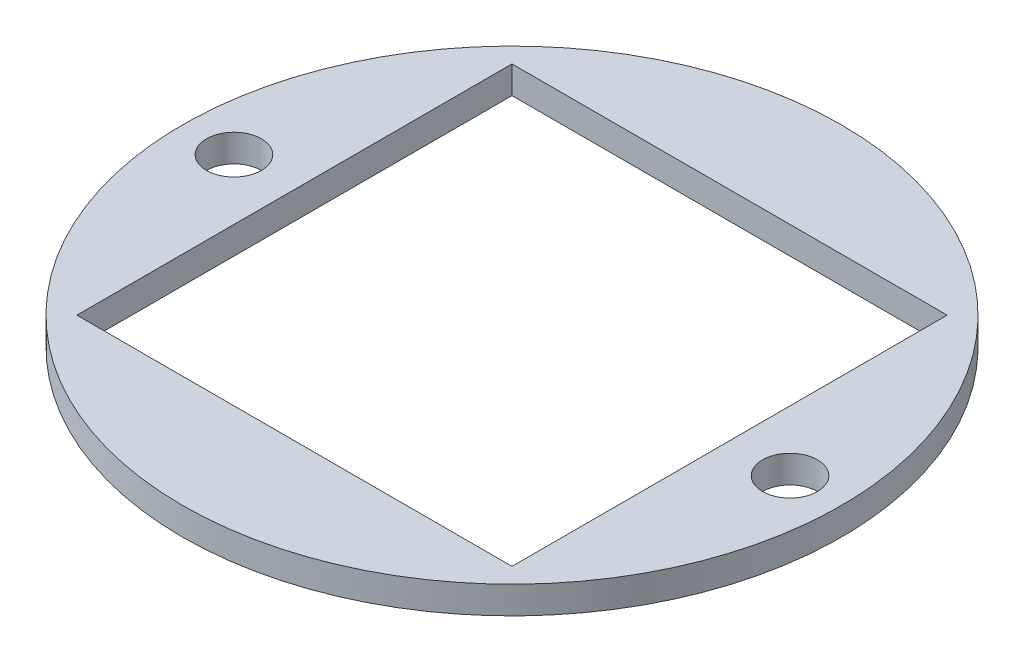
SolidWorks part; units mm, degrees
ref_plane "Front Plane" through (0, 0, 0) normal (0, 0, 1) x (1, 0, 0)
ref_plane "Top Plane" through (0, 0, 0) normal (0, 1, 0) x (1, 0, 0)
ref_plane "Right Plane" through (0, 0, 0) normal (1, 0, 0) x (0, 0, -1)
sketch "Sketch1" plane through (0, 0, 0) normal (0, 1, 0) x (1, 0, 0)
  circle A0 centre (0, 0) radius 76.2
  dimension "D1" = 152.4
extrude "Boss-Extrude1" add sketch "Sketch1" along normal blind 6.35
sketch "Sketch2" plane through (0, 6.35, 0) normal (0, 1, 0) x (1, 0, 0)
  circle A0 centre (0, 0) radius 35
  dimension "D1" = 70
extrude "Cut-Extrude1" cut sketch "Sketch2" against normal blind 3.175
sketch "Sketch3" plane through (0, 6.35, 0) normal (0, 1, 0) x (1, 0, 0)
  line L0 (-76.2, 0) -> (76.2, 0) construction
  line L1 (-51.5875, 51.5875) -> (51.5875, 51.5875) construction
  line L2 (-51.5875, 51.5875) -> (-51.5875, -51.5875) construction
  line L3 (-51.5875, -51.5875) -> (51.5875, -51.5875) construction
  line L4 (51.5875, 51.5875) -> (51.5875, -51.5875) construction
  circle A0 centre (0, 0) radius 76.2 construction
  circle A1 centre (-64.2875, 0) radius 6.35
  circle A2 centre (64.2875, 0) radius 6.35
  dimension "D1" = 12.7
  dimension "D2" = 12.7
  dimension "D3" = 12.7
  dimension "D4" = 12.7
extrude "Cut-Extrude2" cut sketch "Sketch3" against normal blind 10
sketch "Sketch4" plane through (0, 6.35, 0) normal (0, 1, 0) x (1, 0, 0)
  line L1 (50, -50) -> (-50, -50) construction
  line L2 (50, -50) -> (50, 50) construction
  line L3 (50, 50) -> (-50, 50) construction
  line L4 (-50, -50) -> (-50, 50) construction
  line L5 (50, -50) -> (-50, 50) construction
  line L6 (50, 50) -> (-50, -50) construction
  point P0 (0, 0)
  dimension "D1" = 100
  dimension "D2" = 100
sketch "Sketch5" plane through (0, 6.35, 0) normal (0, 1, 0) x (1, 0, 0)
  line L1 (50, -50) -> (-50, -50)
  line L2 (50, -50) -> (50, 50)
  line L3 (50, 50) -> (-50, 50)
  line L4 (-50, -50) -> (-50, 50)
  line L5 (50, -50) -> (-50, 50) construction
  line L6 (50, 50) -> (-50, -50) construction
  point P0 (0, 0)
extrude "Cut-Extrude3" cut sketch "Sketch5" against normal blind 10
fillet "Fillet1" radius 0.5 4 edges at (-50, 3.175, 50) (50, 3.175, 50) (50, 3.175, -50) (-50, 3.175, -50)
sketch "Sketch6" plane through (0, 6.35, 0) normal (0, 1, 0) x (1, 0, 0)
  line L0 (49.5, 50) -> (-49.5, 50) construction
  line L1 (51.5875, -51.5875) -> (-51.5875, -51.5875)
  line L2 (51.5875, -51.5875) -> (51.5875, 51.5875)
  line L3 (51.5875, 51.5875) -> (-51.5875, 51.5875)
  line L4 (-51.5875, -51.5875) -> (-51.5875, 51.5875)
  line L5 (51.5875, -51.5875) -> (-51.5875, 51.5875) construction
  line L6 (51.5875, 51.5875) -> (-51.5875, -51.5875) construction
  line L7 (-50, 49.5) -> (-50, -49.5) construction
  point P0 (0, 0)
  dimension "D1" = 1.5875
  dimension "D2" = 1.5875
extrude "Cut-Extrude4" cut sketch "Sketch6" against normal blind 10
sketch "Sketch7" plane through (0, 6.35, 0) normal (0, 1, 0) x (1, 0, 0)
  line L1 (50.3047, -50.3047) -> (-50.3047, -50.3047)
  line L2 (50.3047, -50.3047) -> (50.3047, 50.3047)
  line L3 (50.3047, 50.3047) -> (-50.3047, 50.3047)
  line L4 (-50.3047, -50.3047) -> (-50.3047, 50.3047)
  line L5 (50.3047, -50.3047) -> (-50.3047, 50.3047) construction
  line L6 (50.3047, 50.3047) -> (-50.3047, -50.3047) construction
  line L7 (51.5875, -51.5875) -> (-51.5875, -51.5875)
  line L8 (51.5875, -51.5875) -> (51.5875, 51.5875)
  line L9 (51.5875, 51.5875) -> (-51.5875, 51.5875)
  line L10 (-51.5875, -51.5875) -> (-51.5875, 51.5875)
  line L11 (51.5875, -51.5875) -> (-51.5875, 51.5875) construction
  line L12 (51.5875, 51.5875) -> (-51.5875, -51.5875) construction
  point P0 (0, 0)
  point P6 (0, 0)
  dimension "D1" = 100.6094
  dimension "D2" = 100.6094
extrude "Boss-Extrude2" add sketch "Sketch7" against normal blind 6.35
